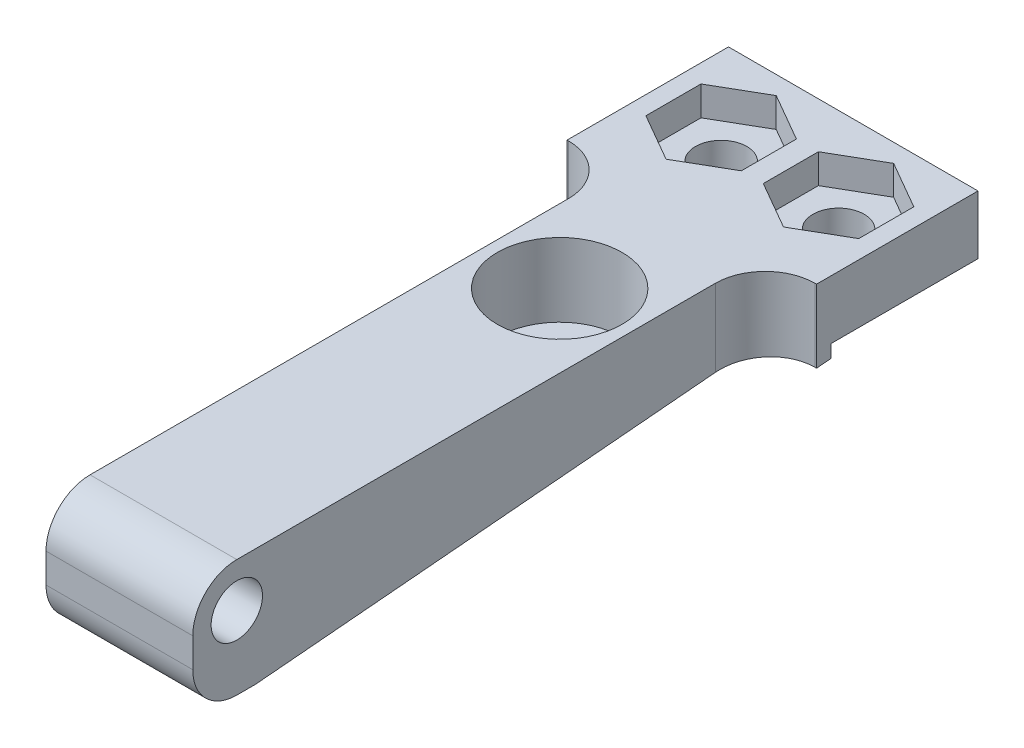
SolidWorks part; units mm, degrees
material "ABS"
ref_plane "Front Plane" through (0, 0, 0) normal (0, 0, 1) x (1, 0, 0)
ref_plane "Top Plane" through (0, 0, 0) normal (0, 1, 0) x (1, 0, 0)
ref_plane "Right Plane" through (0, 0, 0) normal (1, 0, 0) x (0, 0, -1)
sketch "Sketch1" plane through (0, 0, 0) normal (1, 0, 0) x (0, 0, -1)
  line L0 (-3, 0) -> (-3, -5.3744)
  line L4 (0, 3) -> (47, 3)
  line L5 (47, 3) -> (47, -1)
  line L6 (-3, -5.3744) -> (47, -1)
  line L7 (47, -1) -> (37, -1)
  line L8 (-3, 0) -> (0, 0) construction
  line L9 (37, -1) -> (37, -1.8749)
  line L10 (-3, -5) -> (1.2798, -5)
  circle A0 centre (0, 0) radius 1.75
  arc A1 (0, 3) -> (-3, 0) centre (0, 0) ccw
  dimension "D1" = 3.5
  dimension "D2" = 3
  dimension "D3" = 4
  dimension "D4" = 5
  dimension "D5" = 10
  dimension "D6" = 50
  dimension "D7" = 8
extrude "Boss-Extrude1" add sketch "Sketch1" along normal mid plane 17 contours L4 A1 A0 L0 L6 L9 L7 L5 region at (0, -0.2172, -19.5601)
fillet "Fillet1" radius 3 1 edges at (0, -5, 3)
sketch "Sketch2" plane through (0, 3, 0) normal (0, 1, 0) x (1, 0, 0)
  line L0 (-8.5, 42) -> (-4, 42) construction
  line L1 (-8.5, 0) -> (-8.5, 47) construction
  line L2 (-4, 42) -> (4, 42) construction
  line L3 (4, 42) -> (8.5, 42) construction
  line L4 (8.5, 0) -> (8.5, 47) construction
  line L5 (8.5, 47) -> (-8.5, 47) construction
  line L7 (0.75, 40.1236) -> (4, 38.2472)
  line L8 (4, 38.2472) -> (7.25, 40.1236)
  line L9 (7.25, 40.1236) -> (7.25, 43.8764)
  line L10 (7.25, 43.8764) -> (4, 45.7528)
  line L11 (4, 45.7528) -> (0.75, 43.8764)
  line L12 (0.75, 43.8764) -> (0.75, 40.1236)
  line L13 (-0.75, 43.8764) -> (-4, 45.7528)
  line L14 (-4, 45.7528) -> (-7.25, 43.8764)
  line L15 (-7.25, 43.8764) -> (-7.25, 40.1236)
  line L16 (-7.25, 40.1236) -> (-4, 38.2472)
  line L17 (-4, 38.2472) -> (-0.75, 40.1236)
  line L18 (-0.75, 40.1236) -> (-0.75, 43.8764)
  circle A0 centre (-4, 42) radius 1.75
  circle A1 centre (4, 42) radius 1.75
  circle A2 centre (4, 42) radius 3.25 construction
  circle A3 centre (-4, 42) radius 3.25 construction
  dimension "D1" = 3.5
  dimension "D2" = 8
  dimension "7.5" = 5
  dimension "D4" = 6.5
extrude "Cut-Extrude1" cut sketch "Sketch2" against normal through all contours A0 | A1 region at (-4, 3, -42) region at (4, 3, -42)
extrude "Cut-Extrude2" cut sketch "Sketch2<3>" against normal blind 2 contours L11 L12 L7 L8 L9 L10 A1 | L17 L18 L13 L14 L15 L16 A0 region at (0.8493, 3, -42) region at (-0.8493, 3, -42)
sketch "Sketch2<3>" plane through (0, 3, 0) normal (0, 1, 0) x (1, 0, 0) same geometry as "Sketch2"
sketch "Sketch3" plane through (0, 3, 0) normal (0, 1, 0) x (1, 0, 0)
  line L0 (0, 27) -> (0, 0) construction
  line L1 (0, 27) -> (0, 38) construction
  circle A0 centre (0, 27) radius 4.25
  dimension "D3" = 8.5
  dimension "D1" = 38
  dimension "D2" = 11
extrude "Cut-Extrude3" cut sketch "Sketch3" against normal blind 5
sketch "Sketch4" plane through (0, 3, 0) normal (0, 1, 0) x (1, 0, 0)
  line L0 (0, 0) -> (0, 47) construction
  line L1 (8.5, 47) -> (-8.5, 47) construction
  line L2 (8.5, -3) -> (-8.5, -3) construction
  line L3 (5, -3) -> (-5, -3) construction
  line L4 (5, -3) -> (5, 36) construction
  line L5 (5, 36) -> (-5, 36) construction
  line L6 (-5, -3) -> (-5, 36) construction
  line L7 (0, 36) -> (0, -3) construction
  line L8 (5, 16.5) -> (-5, 16.5) construction
  line L9 (-8.5, -3) -> (-5, -3)
  line L10 (-5, -3) -> (-5, 32.6)
  line L11 (-8.4, 36) -> (-8.5, 36)
  line L12 (-8.5, 36) -> (-8.5, -3)
  line L14 (8.4, 36) -> (8.5, 36)
  line L15 (5, -3) -> (5, 32.6)
  line L16 (8.5, -3) -> (5, -3)
  line L17 (8.5, 36) -> (8.5, -3)
  arc A0 (8.4, 36) -> (5, 32.6) centre (8.4, 32.6) ccw
  arc A1 (-5, 32.6) -> (-8.4, 36) centre (-8.4, 32.6) ccw
  point P5 (0, 16.5)
  dimension "D4" = 3.4
  dimension "D1" = 10
  dimension "D2" = 11
  dimension "D3" = 3.5
extrude "Cut-Extrude4" cut sketch "Sketch4" against normal up to next
